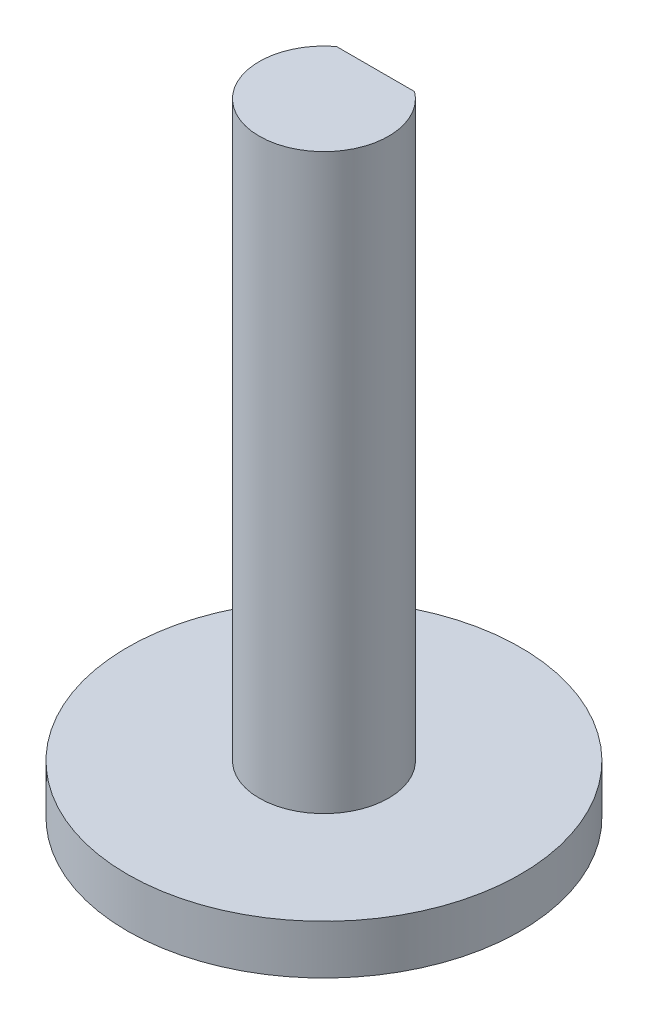
SolidWorks part; units mm, degrees
ref_plane "Alzado" through (0, 0, 0) normal (0, 0, 1) x (1, 0, 0)
ref_plane "Planta" through (0, 0, 0) normal (0, 1, 0) x (1, 0, 0)
ref_plane "Vista lateral" through (0, 0, 0) normal (1, 0, 0) x (0, 0, -1)
sketch "Croquis3" plane through (0, 0, 0) normal (0, 1, 0) x (1, 0, 0)
  circle A0 centre (0, 0) radius 12
  dimension "D1" = 24
extrude "Saliente-Extruir1" add sketch "Croquis3" along normal blind 3
sketch "Croquis4" plane through (0, 3, 0) normal (0, 1, 0) x (1, 0, 0)
  circle A0 centre (0, 0) radius 3.95
  dimension "D1" = 7.9
extrude "Saliente-Extruir2" add sketch "Croquis4" along normal blind 35
sketch "Croquis5" plane through (0, 38, 0) normal (0, 1, 0) x (1, 0, 0)
  line L0 (0, 3.95) -> (0, 3.15) construction
  line L1 (2.3833, 3.15) -> (-2.3833, 3.15)
  circle A0 centre (0, 0) radius 3.95 construction
  arc A1 (2.3833, 3.15) -> (-2.3833, 3.15) centre (0, 0) ccw
  point P5 (0, 0)
  dimension "D1" = 0.8
extrude "Cortar-Extruir1" cut sketch "Croquis5" against normal blind 20
